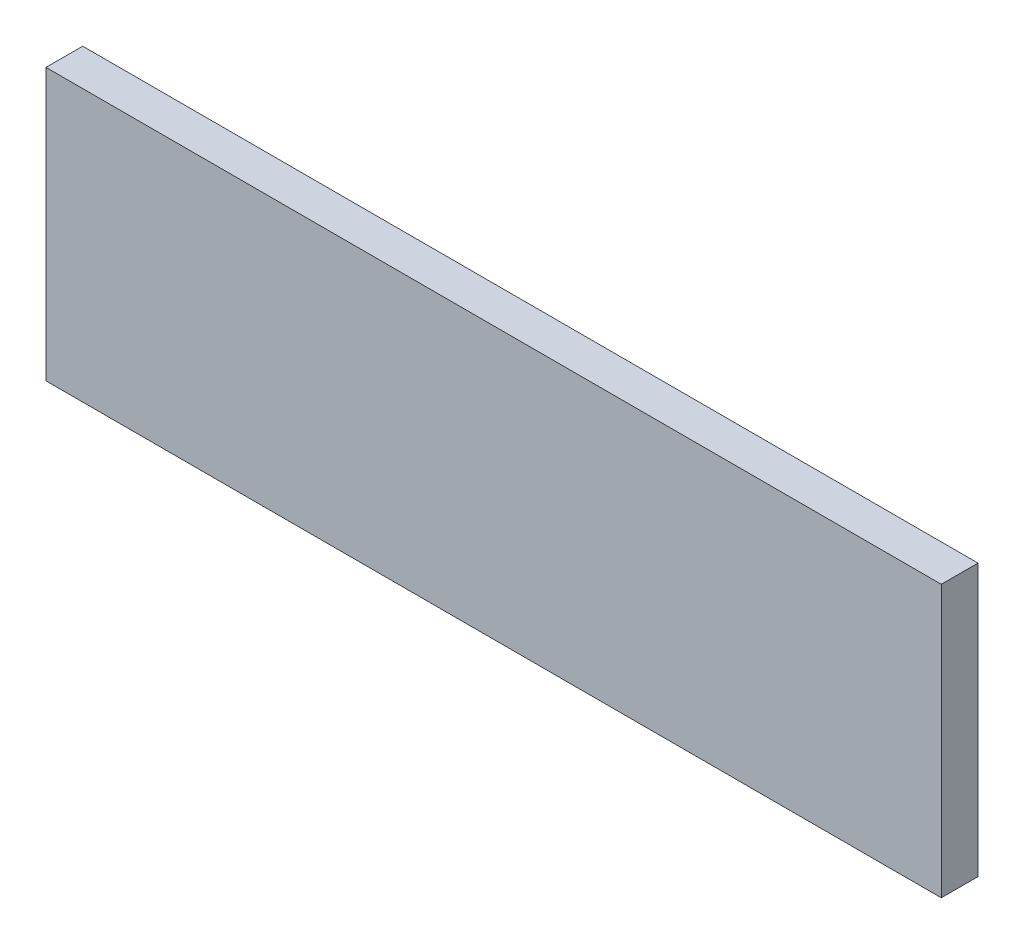
SolidWorks part; units mm, degrees
ref_plane "Front Plane" through (0, 0, 0) normal (0, 0, 1) x (1, 0, 0)
ref_plane "Top Plane" through (0, 0, 0) normal (0, 1, 0) x (1, 0, 0)
ref_plane "Right Plane" through (0, 0, 0) normal (1, 0, 0) x (0, 0, -1)
sketch "Sketch1" plane through (0, 0, 0) normal (0, 0, 1) x (1, 0, 0)
  line L0 (-80.3006, 19.1433) -> (-330.3006, 19.1433) construction
  line L1 (-330.3006, 99.1433) -> (-80.3006, 99.1433) construction
  line L2 (-330.3006, 99.1433) -> (-330.3006, 19.1433) construction
  line L3 (-330.3006, 19.1433) -> (-80.3006, 19.1433) construction
  line L4 (-80.3006, 99.1433) -> (-80.3006, 19.1433) construction
  line L5 (-330.3006, 94.1433) -> (-330.3006, 34.1433) construction
  line L6 (-80.3006, 34.1433) -> (-80.3006, 94.1433) construction
  line L7 (-85.3006, 99.1433) -> (-145.3006, 99.1433) construction
  line L8 (-327.3006, 96.1433) -> (-83.3006, 96.1433)
  line L9 (-83.3006, 96.1433) -> (-83.3006, 22.1433)
  line L10 (-327.3006, 22.1433) -> (-83.3006, 22.1433)
  line L11 (-327.3006, 96.1433) -> (-327.3006, 22.1433)
  dimension "D1" = 3
extrude "Boss-Extrude1" add sketch "Sketch1" along normal blind 10
